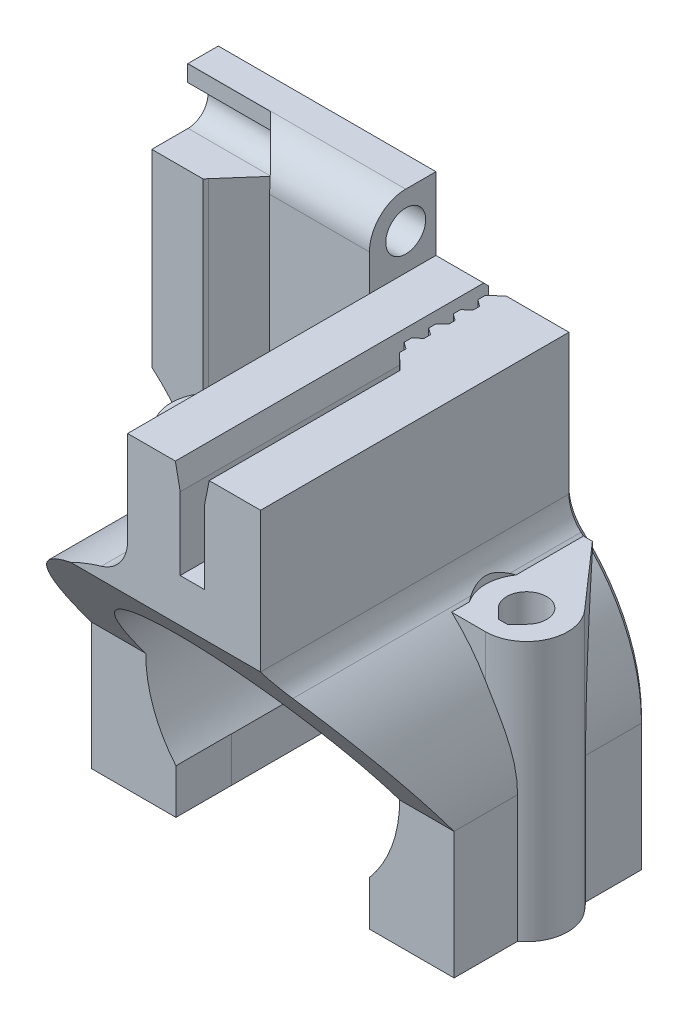
SolidWorks part; units mm, degrees
material "Custom Plastic"
ref_plane "Front Plane" through (0, 0, 0) normal (0, 0, 1) x (1, 0, 0)
ref_plane "Top Plane" through (0, 0, 0) normal (0, 1, 0) x (1, 0, 0)
ref_plane "Right Plane" through (0, 0, 0) normal (1, 0, 0) x (0, 0, -1)
sketch "Sketch1" plane through (0, 0, 0) normal (0, 0, 1) x (1, 0, 0)
  line L0 (-23.622, -10.5) -> (30.4823, -10.5) construction
  line L1 (-23.622, -16.5) -> (30.4823, -16.5) construction
  line L2 (8, -6.8007) -> (8, -10.5)
  line L3 (8, -10.5) -> (15, -10.5)
  line L4 (-15, -10.5) -> (-8, -10.5)
  line L5 (-8, -6.8007) -> (-8, -10.5)
  line L6 (15, 0) -> (15, -10.5)
  line L7 (-2, 25) -> (9, 25)
  line L9 (9, 25) -> (9, 13.4164)
  line L10 (-2, 25) -> (-2, 17.2916)
  line L12 (-15, -10.5) -> (-15, 0)
  arc A0 (-4.1667, 14.4097) -> (-2, 17.2916) centre (-5, 17.2916) ccw
  arc A1 (15, 0) -> (10, 11.1803) centre (0, 0) ccw
  arc A2 (10, 11.1803) -> (9, 13.4164) centre (12, 13.4164) cw
  arc A4 (8, -6.8007) -> (-8, -6.8007) centre (0, 0) ccw
  arc A5 (-4.1667, 14.4097) -> (-15, 0) centre (0, 0) ccw
  dimension "D1" = 16
  dimension "D4" = 25
  dimension "D5" = 2
  dimension "D6" = 21
  dimension "D7" = 4.5
  dimension "D3" = 3
  dimension "D8" = 3
  dimension "D9" = 9
  dimension "D2" = 6
extrude "Boss-Extrude1" add sketch "Sketch1" along normal blind 26
sketch "Sketch4" plane through (0, -10.5, 0) normal (0, -1, 0) x (1, 0, 0)
  line L0 (10.939, 0.5) -> (7.9931, 0.5)
  line L3 (13, 11.4) -> (7.9931, 11.4)
  line L4 (7.9931, 11.4) -> (7.9931, 0.5)
  line L5 (10.939, 0.5) -> (15.5548, 5.7566)
  arc A1 (15.5548, 5.7566) -> (13, 11.4) centre (13, 8) ccw
  dimension "D1" = 3.4
  dimension "D2" = 13
  dimension "D4" = 8
extrude "Boss-Extrude2" add sketch "Sketch4" against normal blind 21.5
sketch "Sketch2" plane through (0, -10.5, 0) normal (0, -1, 0) x (1, 0, 0)
  line L0 (13, 16) -> (13, 0) construction
  circle A0 centre (13, 8) radius 1.65
  arc A3 (15.5548, 5.7566) -> (15, 10.7495) centre (13, 8) ccw construction
  dimension "D1" = 3.3
extrude "Cut-Extrude1" cut sketch "Sketch2" against normal through all
mirror "Mirror1" about plane through (0, 0, 0) normal (1, 0, 0) of "Boss-Extrude2", "Cut-Extrude1"
sketch "Sketch5" plane through (0, -10.5, 0) normal (0, -1, 0) x (1, 0, 0)
  line L0 (-13, 8) -> (-11.8333, 9.1667)
  line L1 (-11.8333, 9.1667) -> (-12.6365, 9.97)
  line L2 (-12.6365, 9.97) -> (-13.3635, 9.97)
  line L3 (-13.3635, 9.97) -> (-14.1667, 9.1667)
  line L4 (-14.1667, 9.1667) -> (-13, 8)
  line L5 (13, 8) -> (14.1667, 9.1667)
  line L6 (14.1667, 9.1667) -> (13.3635, 9.97)
  line L7 (12.6365, 9.97) -> (11.8333, 9.1667)
  line L8 (11.8333, 9.1667) -> (13, 8)
  line L9 (12.6365, 9.97) -> (13.3635, 9.97)
  circle A0 centre (-13, 8) radius 1.65 construction
  circle A1 centre (13, 8) radius 1.65 construction
  point P0 (-13, 9.65)
  point P4 (13, 9.65)
  dimension "D1" = 0.32
  dimension "D2" = 0.32
extrude "Cut-Extrude3" cut sketch "Sketch5" against normal through all
sketch "Sketch7" plane through (0, 25, 0) normal (0, 1, 0) x (1, 0, 0)
  line L0 (3.2, -3.116) -> (3.2, -10.7303) construction
  line L1 (3.45, -2.334) -> (2.9, -1.934)
  line L2 (2.9, -1.934) -> (2.9, -1.334)
  line L19 (4.35, -9.8281) -> (4.35, -26)
  line L22 (3.45, -8.962) -> (4.35, -9.8281)
  line L23 (2.9, -1.334) -> (4.35, 0)
  line L24 (3.45, -8.43) -> (3.45, -8.962)
  line L25 (3.45, -6.398) -> (3.45, -6.93)
  line L26 (3.45, -4.366) -> (3.45, -4.898)
  line L27 (2.9, -8.03) -> (3.45, -8.43)
  line L28 (2.9, -7.43) -> (2.9, -8.03)
  line L29 (3.45, -6.93) -> (2.9, -7.43)
  line L30 (2.9, -5.998) -> (3.45, -6.398)
  line L31 (2.9, -5.398) -> (2.9, -5.998)
  line L32 (3.45, -4.898) -> (2.9, -5.398)
  line L33 (2.9, -3.966) -> (3.45, -4.366)
  line L34 (2.9, -3.366) -> (2.9, -3.966)
  line L35 (3.45, -2.866) -> (2.9, -3.366)
  line L36 (2.35, 0) -> (2.35, -26)
  line L37 (4.35, -26) -> (2.35, -26)
  line L38 (3.45, -2.334) -> (3.45, -2.866)
  line L39 (4.35, 0) -> (2.35, 0)
  point P0 (3.2, -3.116)
  dimension "D1" = 0.6
  dimension "D2" = 0.55
  dimension "D3" = 2.032
  dimension "D4" = 1.1
  dimension "D5" = 2
  dimension "D8" = 3.2
extrude "Cut-Extrude4" cut sketch "Sketch7" against normal blind 8
sketch "Sketch13" plane through (0, 0, 0) normal (0, 0, -1) x (-1, 0, 0)
  line L0 (2, 17.2916) -> (2, 31)
  line L1 (2, 31) -> (20, 31)
  line L2 (20, 31) -> (20, 10.7393)
  line L3 (-2.35, 25) -> (2, 25) construction
  line L4 (15, 0) -> (15, -10.5) construction
  arc A0 (2, 17.2916) -> (4.1667, 14.4097) centre (5, 17.2916) ccw
  arc A1 (15, 0) -> (4.1667, 14.4097) centre (0, 0) ccw
  arc A2 (20, 10.7393) -> (15, 0) centre (29.0333, 0) ccw
  dimension "D1" = 6
  dimension "D2" = 5
extrude "Boss-Extrude4" add sketch "Sketch13" against normal blind 6
sketch "Sketch9" plane through (0, 0, 0) normal (1, 0, 0) x (0, 0, -1)
  line L0 (-26, 13.4164) -> (-16, 0)
  line L1 (-26, 0) -> (-10.7495, 0) construction
  line L2 (-16, 0) -> (-16, -10.5)
  line L3 (-26, -10.5) -> (-10.7495, -10.5) construction
  line L4 (-16, -10.5) -> (-26, -10.5)
  line L5 (-26, -10.5) -> (-26, 13.4164)
  dimension "D1" = 16
extrude "Cut-Extrude5" cut sketch "Sketch9" against normal through all and the other way through all
sketch "Sketch10" plane through (0, 11, 0) normal (0, 1, 0) x (1, 0, 0)
  line L0 (-10.5958, -10.4042) -> (-16.4, -16.2083)
  line L1 (16.4, -8) -> (16.4, -16.2083)
  line L2 (-10.5958, -5.5958) -> (-13.1611, -3.0306)
  line L3 (15, 29.0402) -> (-15, -5.1247) construction
  line L4 (-13.1611, -3.0306) -> (-15.5548, -5.7566)
  line L5 (0, 0) -> (0, -28.6456) construction
  line L6 (13.1611, -3.0306) -> (15.5548, -5.7566)
  line L7 (10.5958, -5.5958) -> (13.1611, -3.0306)
  line L8 (10.5958, -10.4042) -> (16.4, -16.2083)
  line L10 (-16.4, -8) -> (-16.4, -16.2083)
  arc A0 (10.5958, -10.4042) -> (10.5958, -5.5958) centre (13, -8) cw
  arc A1 (-15.5548, -5.7566) -> (-16.4, -8) centre (-13, -8) ccw
  arc A2 (15.5548, -5.7566) -> (16.4, -8) centre (13, -8) cw
  arc A3 (-10.5958, -10.4042) -> (-10.5958, -5.5958) centre (-13, -8) ccw
extrude "Cut-Extrude6" cut sketch "Sketch10" along normal through all
chamfer "Chamfer1" distance 0.4 distance2 2 2 edges at (2.35, 25, 13) (4.35, 25, 17.914) first distance on face at (-0.26, 25, 11.6) first distance on face at (3.8976, 25, 6.8795)
fillet "Fillet1" radius 3 1 edges at (-6.1252, 31, 6)
sketch "Sketch14" plane through (-2, 0, 0) normal (1, 0, 0) x (0, 0, -1)
  circle A0 centre (-3, 28) radius 1.65
  dimension "D1" = 3.3
extrude "Cut-Extrude8" cut sketch "Sketch14" against normal through all
sketch "Sketch15" plane through (-20, 0, 0) normal (-1, 0, 0) x (0, 0, 1)
  line L2 (3, 26.35) -> (6, 26.35)
  line L3 (6, 10.7393) -> (6, 28) construction
  line L4 (6, 26.35) -> (6, 31)
  line L5 (6, 31) -> (3.0306, 31)
  line L6 (3.0306, 29.6497) -> (3.0306, 31)
  arc A0 (3.0306, 29.6497) -> (3, 26.35) centre (3, 28) ccw
extrude "Cut-Extrude9" cut sketch "Sketch15" against normal up to vertex (6.8389 mm away) up to point (-13.1611, 26.3503, 3.0306)
chamfer "Chamfer2" distance 0.5 angle 45 18 edges at (6.675, 25, 0) (9, 19.2082, 0) (9.2614, 12.1917, 0) (13.6931, 6.1237, 0) (15, -5.25, 0) (11.5, -10.5, 0) (8, -8.6504, 0) (0, 10.5, 0) (-8, -8.6504, 0) (-11.5, -10.5, 0) (-15, -5.25, 0) (-16.3113, 5.9231, 0) (-20, 20.8697, 0) (-11, 31, 0) (-2, 28, 0) (3.35, 17, 0) (2.35, 20, 0) (-0.025, 25, 0)
sketch "Sketch16" plane through (0, 0, 0) normal (0, 0, 1) x (1, 0, 0)
  circle A0 centre (0, 0) radius 10.5
  arc A1 (10.5, 0) -> (-10.5, 0) centre (0, 0) ccw construction
extrude "Cut-Extrude11" cut sketch "Sketch16" along normal through all
equation "\"y-cross-rib-thickness\"=6"
equation "\"y-rib-thickness\"=6"
equation "\"bed-plate-thickness\"=6"
equation "\"x-plate-thickness\"=5"
equation "\"rod-diameter\"=12"
equation "\"t-nut-hole-diameter\"=3"
equation "\"y-plate-thickness\"=5"
equation "\"enclosure-thickness\"=0.6"
equation "\"M3-Clearance\"=3.3"
equation "\"M4-Clearance\"=4.3"
equation "\"M5-Clearance\"=5.3"
equation "\"M6-Clearance\"=6.3"
equation "\"M8-Clearance\"=8.3"
equation "\"623-Bearing-Dia\"=11.2"
